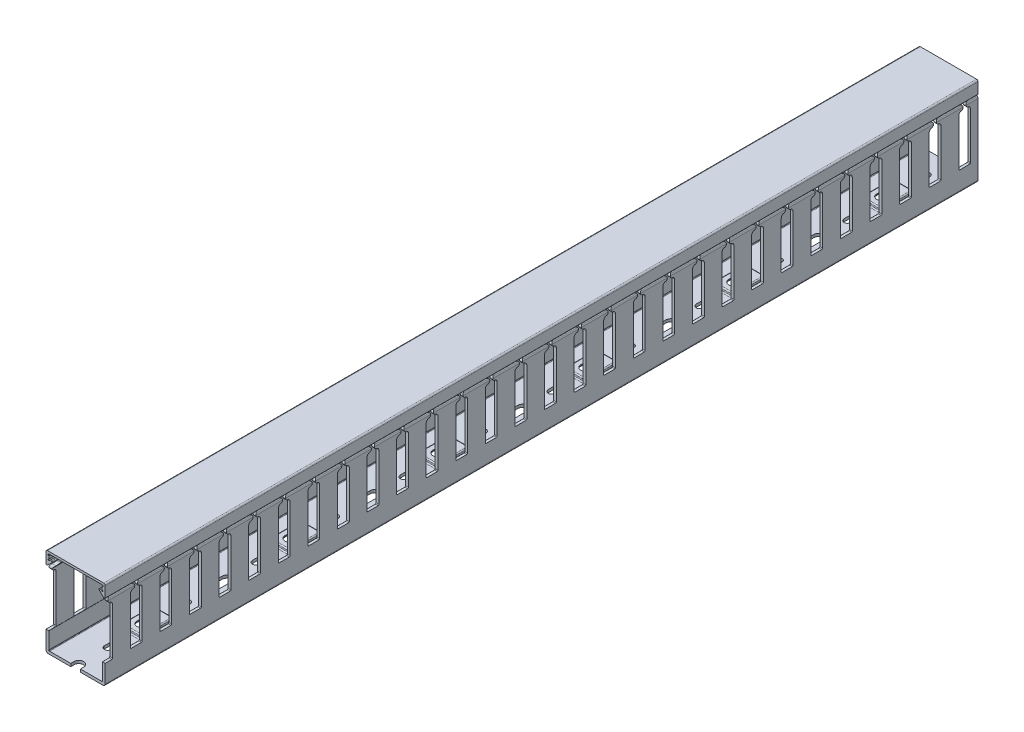
SolidWorks part; units mm, degrees
ref_plane "Front Plane" through (0, 0, 0) normal (0, 0, 1) x (1, 0, 0)
ref_plane "Top Plane" through (0, 0, 0) normal (0, 1, 0) x (1, 0, 0)
ref_plane "Right Plane" through (0, 0, 0) normal (1, 0, 0) x (0, 0, -1)
sketch "Sketch1" plane through (0, 0, 0) normal (0, 0, 1) x (1, 0, 0)
  line L0 (-18.2, -27.85) -> (-17.973, -27.983)
  line L1 (-20, -28.55) -> (-20, 19.1871)
  line L2 (-20, 21.7598) -> (-20, 29.05)
  line L3 (-18.5, 28.35) -> (-18.5, 27.55)
  line L4 (-18.5, 25.25) -> (-18.5, 25.058)
  line L5 (-19.6147, 20.1908) -> (-15.6798, 24.5609)
  line L6 (-17.8221, 24.7703) -> (-17.3671, 25.2097)
  line L7 (-15.9527, 24.4903) -> (-19.1527, 21.4001)
  line L8 (-18.1, 18.8416) -> (-18.1, -16.3923)
  line L9 (-18.1, -16.5077) -> (-18.1, -27.65)
  line L10 (-18, 25.55) -> (-18, 27.25)
  line L11 (-14.8603, 22.6316) -> (-17.9716, 19.1762)
  line L12 (-18.2, -16.45) -> (-18.1, -16.5077)
  line L13 (-13.3, 25.85) -> (-13.3, 24.6071)
  line L14 (-7, -28.15) -> (-7, -25.65)
  line L15 (-18.5, -30.05) -> (18.5, -30.05)
  line L16 (0, -30.05) -> (0, 30.05) construction
  line L18 (-17.6, -28.15) -> (17.6, -28.15)
  line L19 (-17.973, -27.983) -> (-17.973, -27.7208) construction
  line L20 (-18.082, -27.7829) -> (-17.973, -27.7208) construction
  line L21 (18.1, -16.5077) -> (18.1, -16.3923) construction
  line L23 (-7, -25.65) -> (7, -25.65)
  line L24 (-18.1, -16.5077) -> (-18.1, -16.3923) construction
  line L25 (-2.25, -30.05) -> (-2.25, -28.15)
  line L26 (2.25, -30.05) -> (2.25, -28.15)
  line L27 (7, -28.15) -> (7, -25.65)
  line L28 (17.973, -27.717) -> (18.082, -27.7829) construction
  line L29 (-18.1, -16.3923) -> (-18.2, -16.45)
  line L30 (18.1, -16.3923) -> (18.2, -16.45)
  line L31 (-18.082, -27.7829) -> (-18.2, -27.85)
  line L33 (18.4, 25.35) -> (18.2, 25.35)
  line L34 (-16.3, 25.35) -> (-17.0198, 25.35)
  line L35 (-18.4, 25.35) -> (-18.2, 25.35)
  line L36 (16.3, 25.35) -> (17.0198, 25.35)
  line L38 (-18.2, 27.45) -> (-18.4, 27.45)
  line L39 (18.2, 27.45) -> (18.4, 27.45)
  line L40 (16.0883, 27.65) -> (15.1, 27.65)
  line L41 (-16.0883, 27.65) -> (-15.1, 27.65)
  line L42 (-18.3, 28.55) -> (18.3, 28.55)
  line L44 (19, 30.05) -> (-19, 30.05)
  line L46 (-16.3812, 25.7055) -> (-17.6188, 25.3739)
  line L47 (16.3812, 25.7055) -> (17.6188, 25.3739)
  line L48 (13.3, 25.85) -> (13.3, 24.6071)
  line L49 (18, 25.55) -> (18, 27.25)
  line L50 (18.1, 18.8416) -> (18.1, -16.3923)
  line L51 (18.1, -16.5077) -> (18.1, -27.65)
  line L52 (18.5, 28.35) -> (18.5, 27.55)
  line L53 (18.5, 25.25) -> (18.5, 25.058)
  line L54 (18.2, -16.45) -> (18.1, -16.5077)
  line L55 (14.8603, 22.6316) -> (17.9716, 19.1762)
  line L56 (20, -28.55) -> (20, 19.1871)
  line L57 (20, 21.7598) -> (20, 29.05)
  line L58 (15.9527, 24.4903) -> (19.1527, 21.4001)
  line L59 (17.8221, 24.7703) -> (17.3671, 25.2097)
  line L60 (19.6147, 20.1908) -> (15.6798, 24.5609)
  line L61 (18.2, -27.85) -> (17.973, -27.983)
  line L62 (-2.25, -29.1) -> (2.25, -29.1) construction
  line L63 (-7, -26.9) -> (7, -26.9) construction
  line L64 (0, -29.1) -> (0, -26.9) construction
  line L68 (17.973, -27.983) -> (17.973, -27.717) construction
  line L69 (20, -4.6815) -> (18.1, -4.6815) construction
  line L70 (-20, -4.6815) -> (-18.1, -4.6815) construction
  line L71 (18.082, -27.7829) -> (18.2, -27.85)
  line L72 (16.4159, 20.9039) -> (17.8279, 22.1752) construction
  line L73 (18.2, -27.85) -> (17.973, -27.85) construction
  line L74 (20, 19.1871) -> (20, 19.7629) construction
  line L75 (20, 19.7629) -> (19.6147, 20.1908) construction
  line L76 (18.1, 18.8416) -> (18.1, 19.0335) construction
  line L77 (18.1, 19.0335) -> (17.9716, 19.1762) construction
  line L78 (20, 21.7598) -> (20, 20.5819) construction
  line L79 (20, 20.5819) -> (19.1527, 21.4001) construction
  line L80 (18.3, 28.55) -> (18.3, 30.05) construction
  line L81 (18.5, 28.35) -> (20, 28.35) construction
  line L82 (17.5946, 24.99) -> (16.5526, 23.911) construction
  line L83 (14.0985, 26.3171) -> (16.3812, 25.7055) construction
  line L84 (14.0985, 26.3171) -> (15.6798, 24.5609) construction
  line L85 (15.1, 24.6071) -> (15.1, 25.85) construction
  line L86 (15.1, 25.85) -> (16.0883, 25.85) construction
  line L87 (16.0883, 25.85) -> (16.0883, 24.6071) construction
  line L88 (16.0883, 24.6071) -> (15.1, 24.6071) construction
  arc A0 (-20, -28.55) -> (-18.5, -30.05) centre (-18.5, -28.55) ccw
  arc A1 (-18.1, -27.65) -> (-18.082, -27.7829) centre (-17.6, -27.65) ccw
  arc A2 (-17.973, -27.983) -> (-17.6, -28.15) centre (-17.6, -27.65) ccw
  arc A3 (-17.5208, 26.94) -> (-18.1276, 26.6686) centre (-15.7875, 22.25) ccw
  arc A4 (-14.8603, 22.6316) -> (-13.7623, 23.4026) centre (-15.9918, 25.41) ccw
  arc A5 (-16.0883, 27.65) -> (-17.5208, 26.94) centre (-16.0883, 25.85) ccw
  arc A6 (-13.3, 25.85) -> (-15.1, 27.65) centre (-15.1, 25.85) ccw
  arc A7 (-13.7623, 23.4026) -> (-13.3, 24.6071) centre (-15.1, 24.6071) ccw
  arc A8 (-19.6147, 20.1908) -> (-20, 19.1871) centre (-18.5, 19.1871) ccw
  arc A9 (-19, 30.05) -> (-20, 29.05) centre (-19, 29.05) ccw
  arc A10 (-15.6798, 24.5609) -> (-16.3812, 25.7055) centre (-16.2, 25.0293) ccw
  arc A11 (-18.1276, 26.6686) -> (-17.6188, 25.3739) centre (-17.8, 26.05) ccw
  arc A12 (-17.0198, 25.35) -> (-17.3671, 25.2097) centre (-17.0198, 24.85) ccw
  arc A13 (-15.9527, 24.4903) -> (-16.3, 25.35) centre (-16.3, 24.85) ccw
  arc A14 (-20, 21.7598) -> (-19.1527, 21.4001) centre (-19.5, 21.7598) ccw
  arc A15 (-17.9716, 19.1762) -> (-18.1, 18.8416) centre (-17.6, 18.8416) ccw
  arc A16 (-18.5, 25.058) -> (-17.8221, 24.7703) centre (-18.1, 25.058) ccw
  arc A17 (-18.3, 28.55) -> (-18.5, 28.35) centre (-18.3, 28.35) ccw
  arc A18 (-18, 27.25) -> (-18.2, 27.45) centre (-18.2, 27.25) ccw
  arc A19 (-18.2, 25.35) -> (-18, 25.55) centre (-18.2, 25.55) ccw
  arc A20 (-18.4, 25.35) -> (-18.5, 25.25) centre (-18.4, 25.25) ccw
  arc A21 (-18.5, 27.55) -> (-18.4, 27.45) centre (-18.4, 27.55) ccw
  arc A22 (18.5, -30.05) -> (20, -28.55) centre (18.5, -28.55) ccw
  arc A23 (17.6, -28.15) -> (17.973, -27.983) centre (17.6, -27.65) ccw
  arc A24 (18.082, -27.7829) -> (18.1, -27.65) centre (17.6, -27.65) ccw
  arc A25 (18.1276, 26.6686) -> (17.5208, 26.94) centre (15.7875, 22.25) ccw
  arc A26 (13.7623, 23.4026) -> (14.8603, 22.6316) centre (15.9918, 25.41) ccw
  arc A27 (13.3, 24.6071) -> (13.7623, 23.4026) centre (15.1, 24.6071) ccw
  arc A28 (15.1, 27.65) -> (13.3, 25.85) centre (15.1, 25.85) ccw
  arc A29 (17.5208, 26.94) -> (16.0883, 27.65) centre (16.0883, 25.85) ccw
  arc A30 (20, 19.1871) -> (19.6147, 20.1908) centre (18.5, 19.1871) ccw
  arc A31 (20, 29.05) -> (19, 30.05) centre (19, 29.05) ccw
  arc A32 (17.6188, 25.3739) -> (18.1276, 26.6686) centre (17.8, 26.05) ccw
  arc A33 (16.3812, 25.7055) -> (15.6798, 24.5609) centre (16.2, 25.0293) ccw
  arc A34 (17.3671, 25.2097) -> (17.0198, 25.35) centre (17.0198, 24.85) ccw
  arc A35 (16.3, 25.35) -> (15.9527, 24.4903) centre (16.3, 24.85) ccw
  arc A36 (19.1527, 21.4001) -> (20, 21.7598) centre (19.5, 21.7598) ccw
  arc A37 (18.1, 18.8416) -> (17.9716, 19.1762) centre (17.6, 18.8416) ccw
  arc A38 (17.8221, 24.7703) -> (18.5, 25.058) centre (18.1, 25.058) ccw
  arc A39 (18.5, 28.35) -> (18.3, 28.55) centre (18.3, 28.35) ccw
  arc A40 (18.2, 27.45) -> (18, 27.25) centre (18.2, 27.25) ccw
  arc A41 (18, 25.55) -> (18.2, 25.35) centre (18.2, 25.55) ccw
  arc A42 (18.5, 25.25) -> (18.4, 25.35) centre (18.4, 25.25) ccw
  arc A43 (18.4, 27.45) -> (18.5, 27.55) centre (18.4, 27.55) ccw
  point P188 (0, 28.55)
  dimension "D2" = 1.5
  dimension "D9" = 0.5
  dimension "D12" = 1
  dimension "D13" = 1.8
  dimension "D14" = 0.2
  dimension "D15" = 0.1
  dimension "D16" = 0.7
  dimension "D28" = 0.4
  dimension "D29" = 3
  dimension "D30" = 5
  dimension "D1" = 14
  dimension "Height" = 60.1
  dimension "Width" = 40
  dimension "D3" = 1.9
  dimension "D4" = 1.5
  dimension "D5" = 0.1155
  dimension "D6" = 46
  dimension "D7" = 138
  dimension "D10" = 2.5
  dimension "D11" = 4.5
  dimension "D18" = 0.3
  dimension "D19" = 0.266
  dimension "D20" = 60
  dimension "D21" = 8.6165
  dimension "D22" = 9.4681
  dimension "D23" = 0.5
  dimension "D24" = 1.1
  dimension "D25" = 2.1
  dimension "D26" = 0.9
  dimension "D27" = 4.8
  dimension "D31" = 0.9883
  dimension "D32" = 1.2429
  dimension "D33" = 33
  dimension "D34" = 5.0184
  dimension "D35" = 4.2208
  dimension "Slot Height" = 13.6
sketch "Sketch2" plane through (0, 0, 0) normal (0, 1, 0) x (1, 0, 0)
  line L1 (-20, 295) -> (20, 295)
  line L2 (-20, 295) -> (-20, -295)
  line L3 (-20, -295) -> (20, -295)
  line L4 (20, 295) -> (20, -295)
  line L5 (-20, 295) -> (20, -295) construction
  line L6 (-20, -295) -> (20, 295) construction
  line L9 (0, -300.25) -> (0, -292.75) construction
  line L10 (-3.25, -300.25) -> (-3.25, -292.75)
  line L11 (3.25, -300.25) -> (3.25, -292.75)
  line L15 (0, -289.5) -> (0, -292.75) construction
  line L16 (0, -300.25) -> (0, -303.5) construction
  line L17 (0, -273.25) -> (0, -269.75) construction
  line L18 (-2.25, -273.25) -> (-2.25, -269.75)
  line L19 (2.25, -273.25) -> (2.25, -269.75)
  line L23 (0, -273.25) -> (0, -275.5) construction
  line L24 (0, -250.25) -> (0, -242.75) construction
  line L26 (0, -269.75) -> (0, -267.5) construction
  line L30 (7, -257.2071) -> (-7, -257.2071)
  line L31 (7, -257.2071) -> (7, -235.7929)
  line L32 (7, -235.7929) -> (-7, -235.7929)
  line L33 (-7, -257.2071) -> (-7, -235.7929)
  line L34 (-3.25, -250.25) -> (-3.25, -242.75)
  line L35 (3.25, -250.25) -> (3.25, -242.75)
  line L36 (0, -200.25) -> (0, -192.75) construction
  line L37 (-3.25, -200.25) -> (-3.25, -192.75)
  line L38 (3.25, -200.25) -> (3.25, -192.75)
  line L45 (0, -223.25) -> (0, -219.75) construction
  line L46 (-2.25, -223.25) -> (-2.25, -219.75)
  line L47 (2.25, -223.25) -> (2.25, -219.75)
  arc A2 (-3.25, -300.25) -> (3.25, -300.25) centre (0, -300.25) ccw
  arc A3 (3.25, -292.75) -> (-3.25, -292.75) centre (0, -292.75) ccw
  arc A6 (-2.25, -273.25) -> (2.25, -273.25) centre (0, -273.25) ccw
  arc A7 (2.25, -269.75) -> (-2.25, -269.75) centre (0, -269.75) ccw
  arc A10 (-3.25, -250.25) -> (3.25, -250.25) centre (0, -250.25) ccw
  arc A11 (3.25, -242.75) -> (-3.25, -242.75) centre (0, -242.75) ccw
  arc A12 (-3.25, -200.25) -> (3.25, -200.25) centre (0, -200.25) ccw
  arc A13 (3.25, -192.75) -> (-3.25, -192.75) centre (0, -192.75) ccw
  arc A18 (-2.25, -223.25) -> (2.25, -223.25) centre (0, -223.25) ccw
  arc A19 (2.25, -219.75) -> (-2.25, -219.75) centre (0, -219.75) ccw
  point P0 (0, 0)
  point P14 (0, -296.5)
  point P33 (0, -271.5)
  point P67 (0, -246.5)
  point P74 (-7, -246.5)
  point P75 (0, -196.5)
  point P96 (0, -221.5)
  dimension "D1" = 5.5
  dimension "D2" = 14
  dimension "Length" = 590
  dimension "D3" = 6.5
  dimension "D4" = 8
  dimension "D5" = 23.5
  dimension "D6" = 21.4142
  dimension "D7" = 25
  dimension "Slot Spacing 2" = 100
  dimension "Slot Spacing 1" = 50
sketch "Sketch3" plane through (0, 0, 0) normal (0, 0, 1) x (1, 0, 0)
  line L0 (15.9527, 24.4903) -> (19.1527, 21.4001) construction
  line L1 (16.3, 25.35) -> (17.0198, 25.35) construction
  line L2 (17.8221, 24.7703) -> (17.3671, 25.2097) construction
  line L3 (18.5, 25.25) -> (18.5, 25.058) construction
  line L4 (18.4, 25.35) -> (18.2, 25.35) construction
  line L5 (18, 25.55) -> (18, 27.25) construction
  line L6 (18.2, 27.45) -> (18.4, 27.45) construction
  line L7 (18.5, 28.35) -> (18.5, 27.55) construction
  line L8 (20, 21.7598) -> (20, 29.05) construction
  line L9 (19, 30.05) -> (-19, 30.05) construction
  line L10 (-18.3, 28.55) -> (18.3, 28.55) construction
  line L11 (-18.5, 28.35) -> (-18.5, 27.55) construction
  line L12 (-18.2, 27.45) -> (-18.4, 27.45) construction
  line L13 (-18, 25.55) -> (-18, 27.25) construction
  line L14 (-18.4, 25.35) -> (-18.2, 25.35) construction
  line L15 (-18.5, 25.25) -> (-18.5, 25.058) construction
  line L16 (-17.8221, 24.7703) -> (-17.3671, 25.2097) construction
  line L17 (-16.3, 25.35) -> (-17.0198, 25.35) construction
  line L18 (-15.9527, 24.4903) -> (-19.1527, 21.4001) construction
  line L19 (-20, 21.7598) -> (-20, 29.05) construction
  line L20 (15.9527, 24.4903) -> (19.1527, 21.4001)
  line L21 (16.3, 25.35) -> (17.0198, 25.35)
  line L22 (17.8221, 24.7703) -> (17.3671, 25.2097)
  line L23 (18.5, 25.25) -> (18.5, 25.058)
  line L24 (18.4, 25.35) -> (18.2, 25.35)
  line L25 (18, 25.55) -> (18, 27.25)
  line L26 (18.2, 27.45) -> (18.4, 27.45)
  line L27 (18.5, 28.35) -> (18.5, 27.55)
  line L28 (20, 21.7598) -> (20, 29.05)
  line L29 (19, 30.05) -> (-19, 30.05)
  line L30 (-18.3, 28.55) -> (18.3, 28.55)
  line L31 (-18.5, 28.35) -> (-18.5, 27.55)
  line L32 (-18.2, 27.45) -> (-18.4, 27.45)
  line L33 (-18, 25.55) -> (-18, 27.25)
  line L34 (-18.4, 25.35) -> (-18.2, 25.35)
  line L35 (-18.5, 25.25) -> (-18.5, 25.058)
  line L36 (-17.8221, 24.7703) -> (-17.3671, 25.2097)
  line L37 (-16.3, 25.35) -> (-17.0198, 25.35)
  line L38 (-15.9527, 24.4903) -> (-19.1527, 21.4001)
  line L39 (-20, 21.7598) -> (-20, 29.05)
  arc A0 (19.1527, 21.4001) -> (20, 21.7598) centre (19.5, 21.7598) ccw construction
  arc A1 (16.3, 25.35) -> (15.9527, 24.4903) centre (16.3, 24.85) ccw construction
  arc A2 (17.3671, 25.2097) -> (17.0198, 25.35) centre (17.0198, 24.85) ccw construction
  arc A3 (17.8221, 24.7703) -> (18.5, 25.058) centre (18.1, 25.058) ccw construction
  arc A4 (18.5, 25.25) -> (18.4, 25.35) centre (18.4, 25.25) ccw construction
  arc A5 (18, 25.55) -> (18.2, 25.35) centre (18.2, 25.55) ccw construction
  arc A6 (18.2, 27.45) -> (18, 27.25) centre (18.2, 27.25) ccw construction
  arc A7 (18.4, 27.45) -> (18.5, 27.55) centre (18.4, 27.55) ccw construction
  arc A8 (18.5, 28.35) -> (18.3, 28.55) centre (18.3, 28.35) ccw construction
  arc A9 (20, 29.05) -> (19, 30.05) centre (19, 29.05) ccw construction
  arc A10 (-18.3, 28.55) -> (-18.5, 28.35) centre (-18.3, 28.35) ccw construction
  arc A11 (-18.5, 27.55) -> (-18.4, 27.45) centre (-18.4, 27.55) ccw construction
  arc A12 (-18, 27.25) -> (-18.2, 27.45) centre (-18.2, 27.25) ccw construction
  arc A13 (-18.2, 25.35) -> (-18, 25.55) centre (-18.2, 25.55) ccw construction
  arc A14 (-18.4, 25.35) -> (-18.5, 25.25) centre (-18.4, 25.25) ccw construction
  arc A15 (-18.5, 25.058) -> (-17.8221, 24.7703) centre (-18.1, 25.058) ccw construction
  arc A16 (-17.0198, 25.35) -> (-17.3671, 25.2097) centre (-17.0198, 24.85) ccw construction
  arc A17 (-15.9527, 24.4903) -> (-16.3, 25.35) centre (-16.3, 24.85) ccw construction
  arc A18 (-20, 21.7598) -> (-19.1527, 21.4001) centre (-19.5, 21.7598) ccw construction
  arc A19 (-19, 30.05) -> (-20, 29.05) centre (-19, 29.05) ccw construction
  arc A20 (19.1527, 21.4001) -> (20, 21.7598) centre (19.5, 21.7598) ccw
  arc A21 (16.3, 25.35) -> (15.9527, 24.4903) centre (16.3, 24.85) ccw
  arc A22 (17.3671, 25.2097) -> (17.0198, 25.35) centre (17.0198, 24.85) ccw
  arc A23 (17.8221, 24.7703) -> (18.5, 25.058) centre (18.1, 25.058) ccw
  arc A24 (18.5, 25.25) -> (18.4, 25.35) centre (18.4, 25.25) ccw
  arc A25 (18, 25.55) -> (18.2, 25.35) centre (18.2, 25.55) ccw
  arc A26 (18.2, 27.45) -> (18, 27.25) centre (18.2, 27.25) ccw
  arc A27 (18.4, 27.45) -> (18.5, 27.55) centre (18.4, 27.55) ccw
  arc A28 (18.5, 28.35) -> (18.3, 28.55) centre (18.3, 28.35) ccw
  arc A29 (20, 29.05) -> (19, 30.05) centre (19, 29.05) ccw
  arc A30 (-18.3, 28.55) -> (-18.5, 28.35) centre (-18.3, 28.35) ccw
  arc A31 (-18.5, 27.55) -> (-18.4, 27.45) centre (-18.4, 27.55) ccw
  arc A32 (-18, 27.25) -> (-18.2, 27.45) centre (-18.2, 27.25) ccw
  arc A33 (-18.2, 25.35) -> (-18, 25.55) centre (-18.2, 25.55) ccw
  arc A34 (-18.4, 25.35) -> (-18.5, 25.25) centre (-18.4, 25.25) ccw
  arc A35 (-18.5, 25.058) -> (-17.8221, 24.7703) centre (-18.1, 25.058) ccw
  arc A36 (-17.0198, 25.35) -> (-17.3671, 25.2097) centre (-17.0198, 24.85) ccw
  arc A37 (-15.9527, 24.4903) -> (-16.3, 25.35) centre (-16.3, 24.85) ccw
  arc A38 (-20, 21.7598) -> (-19.1527, 21.4001) centre (-19.5, 21.7598) ccw
  arc A39 (-19, 30.05) -> (-20, 29.05) centre (-19, 29.05) ccw
extrude "Boss-Extrude1" add sketch "Sketch3" along normal up to vertex (295 mm away) from vertex separate body up to point (20, 0, 295) starting at point (20, 0, -295)
sketch "Sketch4" plane through (0, 0, 0) normal (0, 0, 1) x (1, 0, 0)
  line L0 (18.2, -27.85) -> (17.973, -27.983) construction
  line L1 (18.082, -27.7829) -> (18.2, -27.85) construction
  line L2 (18.1, -16.5077) -> (18.1, -27.65) construction
  line L3 (18.2, -16.45) -> (18.1, -16.5077) construction
  line L4 (18.1, -16.3923) -> (18.2, -16.45) construction
  line L5 (20, -28.55) -> (20, 19.1871) construction
  line L6 (18.1, 18.8416) -> (18.1, -16.3923) construction
  line L7 (19.6147, 20.1908) -> (15.6798, 24.5609) construction
  line L8 (16.3812, 25.7055) -> (17.6188, 25.3739) construction
  line L9 (14.8603, 22.6316) -> (17.9716, 19.1762) construction
  line L10 (13.3, 25.85) -> (13.3, 24.6071) construction
  line L11 (16.0883, 27.65) -> (15.1, 27.65) construction
  line L12 (-16.3812, 25.7055) -> (-17.6188, 25.3739) construction
  line L13 (-16.0883, 27.65) -> (-15.1, 27.65) construction
  line L14 (-13.3, 25.85) -> (-13.3, 24.6071) construction
  line L15 (-19.6147, 20.1908) -> (-15.6798, 24.5609) construction
  line L16 (-14.8603, 22.6316) -> (-17.9716, 19.1762) construction
  line L17 (-18.1, 18.8416) -> (-18.1, -16.3923) construction
  line L18 (-18.1, -16.3923) -> (-18.2, -16.45) construction
  line L19 (-18.2, -16.45) -> (-18.1, -16.5077) construction
  line L20 (-18.1, -16.5077) -> (-18.1, -27.65) construction
  line L21 (-18.082, -27.7829) -> (-18.2, -27.85) construction
  line L22 (-18.2, -27.85) -> (-17.973, -27.983) construction
  line L23 (-17.6, -28.15) -> (17.6, -28.15) construction
  line L24 (-18.5, -30.05) -> (18.5, -30.05) construction
  line L25 (-20, -28.55) -> (-20, 19.1871) construction
  line L26 (18.2, -27.85) -> (17.973, -27.983)
  line L27 (18.082, -27.7829) -> (18.2, -27.85)
  line L28 (18.1, -16.5077) -> (18.1, -27.65)
  line L29 (18.2, -16.45) -> (18.1, -16.5077)
  line L30 (18.1, -16.3923) -> (18.2, -16.45)
  line L31 (20, -28.55) -> (20, 19.1871)
  line L32 (18.1, 18.8416) -> (18.1, -16.3923)
  line L33 (19.6147, 20.1908) -> (15.6798, 24.5609)
  line L34 (16.3812, 25.7055) -> (17.6188, 25.3739)
  line L35 (14.8603, 22.6316) -> (17.9716, 19.1762)
  line L36 (13.3, 25.85) -> (13.3, 24.6071)
  line L37 (16.0883, 27.65) -> (15.1, 27.65)
  line L38 (-16.3812, 25.7055) -> (-17.6188, 25.3739)
  line L39 (-16.0883, 27.65) -> (-15.1, 27.65)
  line L40 (-13.3, 25.85) -> (-13.3, 24.6071)
  line L41 (-19.6147, 20.1908) -> (-15.6798, 24.5609)
  line L42 (-14.8603, 22.6316) -> (-17.9716, 19.1762)
  line L43 (-18.1, 18.8416) -> (-18.1, -16.3923)
  line L44 (-18.1, -16.3923) -> (-18.2, -16.45)
  line L45 (-18.2, -16.45) -> (-18.1, -16.5077)
  line L46 (-18.1, -16.5077) -> (-18.1, -27.65)
  line L47 (-18.082, -27.7829) -> (-18.2, -27.85)
  line L48 (-18.2, -27.85) -> (-17.973, -27.983)
  line L49 (-17.6, -28.15) -> (17.6, -28.15)
  line L50 (-18.5, -30.05) -> (18.5, -30.05)
  line L51 (-20, -28.55) -> (-20, 19.1871)
  arc A0 (18.5, -30.05) -> (20, -28.55) centre (18.5, -28.55) ccw construction
  arc A1 (17.6, -28.15) -> (17.973, -27.983) centre (17.6, -27.65) ccw construction
  arc A2 (18.082, -27.7829) -> (18.1, -27.65) centre (17.6, -27.65) ccw construction
  arc A3 (18.1, 18.8416) -> (17.9716, 19.1762) centre (17.6, 18.8416) ccw construction
  arc A4 (20, 19.1871) -> (19.6147, 20.1908) centre (18.5, 19.1871) ccw construction
  arc A5 (16.3812, 25.7055) -> (15.6798, 24.5609) centre (16.2, 25.0293) ccw construction
  arc A6 (13.7623, 23.4026) -> (14.8603, 22.6316) centre (15.9918, 25.41) ccw construction
  arc A7 (13.3, 24.6071) -> (13.7623, 23.4026) centre (15.1, 24.6071) ccw construction
  arc A8 (15.1, 27.65) -> (13.3, 25.85) centre (15.1, 25.85) ccw construction
  arc A9 (17.5208, 26.94) -> (16.0883, 27.65) centre (16.0883, 25.85) ccw construction
  arc A10 (18.1276, 26.6686) -> (17.5208, 26.94) centre (15.7875, 22.25) ccw construction
  arc A11 (17.6188, 25.3739) -> (18.1276, 26.6686) centre (17.8, 26.05) ccw construction
  arc A12 (-15.6798, 24.5609) -> (-16.3812, 25.7055) centre (-16.2, 25.0293) ccw construction
  arc A13 (-18.1276, 26.6686) -> (-17.6188, 25.3739) centre (-17.8, 26.05) ccw construction
  arc A14 (-17.5208, 26.94) -> (-18.1276, 26.6686) centre (-15.7875, 22.25) ccw construction
  arc A15 (-16.0883, 27.65) -> (-17.5208, 26.94) centre (-16.0883, 25.85) ccw construction
  arc A16 (-13.3, 25.85) -> (-15.1, 27.65) centre (-15.1, 25.85) ccw construction
  arc A17 (-13.7623, 23.4026) -> (-13.3, 24.6071) centre (-15.1, 24.6071) ccw construction
  arc A18 (-14.8603, 22.6316) -> (-13.7623, 23.4026) centre (-15.9918, 25.41) ccw construction
  arc A19 (-17.9716, 19.1762) -> (-18.1, 18.8416) centre (-17.6, 18.8416) ccw construction
  arc A20 (-19.6147, 20.1908) -> (-20, 19.1871) centre (-18.5, 19.1871) ccw construction
  arc A21 (-18.1, -27.65) -> (-18.082, -27.7829) centre (-17.6, -27.65) ccw construction
  arc A22 (-17.973, -27.983) -> (-17.6, -28.15) centre (-17.6, -27.65) ccw construction
  arc A23 (-20, -28.55) -> (-18.5, -30.05) centre (-18.5, -28.55) ccw construction
  arc A24 (18.5, -30.05) -> (20, -28.55) centre (18.5, -28.55) ccw
  arc A25 (17.6, -28.15) -> (17.973, -27.983) centre (17.6, -27.65) ccw
  arc A26 (18.082, -27.7829) -> (18.1, -27.65) centre (17.6, -27.65) ccw
  arc A27 (18.1, 18.8416) -> (17.9716, 19.1762) centre (17.6, 18.8416) ccw
  arc A28 (20, 19.1871) -> (19.6147, 20.1908) centre (18.5, 19.1871) ccw
  arc A29 (16.3812, 25.7055) -> (15.6798, 24.5609) centre (16.2, 25.0293) ccw
  arc A30 (13.7623, 23.4026) -> (14.8603, 22.6316) centre (15.9918, 25.41) ccw
  arc A31 (13.3, 24.6071) -> (13.7623, 23.4026) centre (15.1, 24.6071) ccw
  arc A32 (15.1, 27.65) -> (13.3, 25.85) centre (15.1, 25.85) ccw
  arc A33 (17.5208, 26.94) -> (16.0883, 27.65) centre (16.0883, 25.85) ccw
  arc A34 (18.1276, 26.6686) -> (17.5208, 26.94) centre (15.7875, 22.25) ccw
  arc A35 (17.6188, 25.3739) -> (18.1276, 26.6686) centre (17.8, 26.05) ccw
  arc A36 (-15.6798, 24.5609) -> (-16.3812, 25.7055) centre (-16.2, 25.0293) ccw
  arc A37 (-18.1276, 26.6686) -> (-17.6188, 25.3739) centre (-17.8, 26.05) ccw
  arc A38 (-17.5208, 26.94) -> (-18.1276, 26.6686) centre (-15.7875, 22.25) ccw
  arc A39 (-16.0883, 27.65) -> (-17.5208, 26.94) centre (-16.0883, 25.85) ccw
  arc A40 (-13.3, 25.85) -> (-15.1, 27.65) centre (-15.1, 25.85) ccw
  arc A41 (-13.7623, 23.4026) -> (-13.3, 24.6071) centre (-15.1, 24.6071) ccw
  arc A42 (-14.8603, 22.6316) -> (-13.7623, 23.4026) centre (-15.9918, 25.41) ccw
  arc A43 (-17.9716, 19.1762) -> (-18.1, 18.8416) centre (-17.6, 18.8416) ccw
  arc A44 (-19.6147, 20.1908) -> (-20, 19.1871) centre (-18.5, 19.1871) ccw
  arc A45 (-18.1, -27.65) -> (-18.082, -27.7829) centre (-17.6, -27.65) ccw
  arc A46 (-17.973, -27.983) -> (-17.6, -28.15) centre (-17.6, -27.65) ccw
  arc A47 (-20, -28.55) -> (-18.5, -30.05) centre (-18.5, -28.55) ccw
extrude "Boss-Extrude2" add sketch "Sketch4" along normal up to vertex (295 mm away) from vertex separate body up to point (20, 0, 295) starting at point (20, 0, -295)
sketch "Sketch5" plane through (0, 0, 0) normal (0, 1, 0) x (1, 0, 0)
  line L4 (7, -235.7929) -> (-7, -235.7929) construction
  line L5 (7, -257.2071) -> (7, -235.7929) construction
  line L6 (7, -257.2071) -> (-7, -257.2071) construction
  line L7 (-7, -257.2071) -> (-7, -235.7929) construction
  line L12 (7, -235.7929) -> (-7, -235.7929)
  line L13 (7, -257.2071) -> (7, -235.7929)
  line L14 (7, -257.2071) -> (-7, -257.2071)
  line L15 (-7, -257.2071) -> (-7, -235.7929)
extrude "Boss-Extrude3" add sketch "Sketch5" along normal up to vertex (-25.65 mm away) from vertex up to point (7, -25.65, 0) starting at point (0, -30.05, 0)
sketch "Sketch6" plane through (0, 0, 0) normal (0, 1, 0) x (1, 0, 0)
  line L4 (-7, -257.2071) -> (-7, -235.7929) construction
  line L5 (7, -235.7929) -> (-7, -235.7929) construction
  line L6 (7, -257.2071) -> (7, -235.7929) construction
  line L7 (7, -257.2071) -> (-7, -257.2071) construction
  line L12 (-7, -257.2071) -> (-7, -235.7929) construction
  line L13 (7, -235.7929) -> (-7, -235.7929) construction
  line L14 (7, -257.2071) -> (7, -235.7929) construction
  line L15 (7, -257.2071) -> (-7, -257.2071) construction
  line L16 (6.268, -256.4751) -> (6.268, -236.5249)
  line L17 (6.268, -236.5249) -> (-6.268, -236.5249)
  line L18 (-6.268, -256.4751) -> (-6.268, -236.5249)
  line L19 (6.268, -256.4751) -> (-6.268, -256.4751)
  dimension "D1" = 0.732
extrude "Cut-Extrude1" cut sketch "Sketch6" along normal blind 3.6678 from vertex starting at point (0, -30.05, 0)
fillet "Fillet1" radius 0.732 24 edges at (0, -28.15, 235.7929) (7, -26.9, 235.7929) (7, -28.15, 246.5) (-7, -28.15, 246.5) (-7, -26.9, 235.7929) (7, -26.9, 257.2071) (0, -28.15, 257.2071) (-7, -26.9, 257.2071) (0, -25.65, 257.2071) (-7, -25.65, 246.5) (0, -25.65, 235.7929) (7, -25.65, 246.5) (0, -26.3822, 236.5249) (0, -30.05, 236.5249) (-6.268, -26.3822, 246.5) (-6.268, -30.05, 246.5) (0, -26.3822, 256.4751) (0, -30.05, 256.4751) (6.268, -26.3822, 246.5) (6.268, -30.05, 246.5) (-6.268, -28.2161, 236.5249) (-6.268, -28.2161, 256.4751) (6.268, -28.2161, 236.5249) (6.268, -28.2161, 256.4751)
pattern_linear "LPattern1" count 6 spacing 100 along (0, 0, -1) of "Boss-Extrude3", "Cut-Extrude1", "Fillet1"
sketch "Sketch7" plane through (0, 0, 0) normal (0, 1, 0) x (1, 0, 0)
  line L4 (-2.25, -223.25) -> (-2.25, -219.75) construction
  line L6 (-3.25, -250.25) -> (-3.25, -242.75) construction
  line L7 (-2.25, -273.25) -> (-2.25, -269.75) construction
  line L10 (-3.25, -300.25) -> (-3.25, -292.75) construction
  line L16 (-2.25, -223.25) -> (-2.25, -219.75)
  line L18 (-3.25, -250.25) -> (-3.25, -242.75)
  line L19 (-2.25, -273.25) -> (-2.25, -269.75)
  line L22 (-3.25, -300.25) -> (-3.25, -292.75)
  line L28 (2.25, -223.25) -> (2.25, -219.75) construction
  line L30 (3.25, -250.25) -> (3.25, -242.75) construction
  line L31 (2.25, -273.25) -> (2.25, -269.75) construction
  line L34 (3.25, -300.25) -> (3.25, -292.75) construction
  line L40 (2.25, -223.25) -> (2.25, -219.75)
  line L42 (3.25, -250.25) -> (3.25, -242.75)
  line L43 (2.25, -273.25) -> (2.25, -269.75)
  line L46 (3.25, -300.25) -> (3.25, -292.75)
  line L54 (0, -271.5) -> (0, -221.5) construction
  arc A8 (-2.25, -223.25) -> (2.25, -223.25) centre (0, -223.25) ccw construction
  arc A9 (2.25, -219.75) -> (-2.25, -219.75) centre (0, -219.75) ccw construction
  arc A12 (-3.25, -250.25) -> (3.25, -250.25) centre (0, -250.25) ccw construction
  arc A13 (3.25, -242.75) -> (-3.25, -242.75) centre (0, -242.75) ccw construction
  arc A14 (-2.25, -273.25) -> (2.25, -273.25) centre (0, -273.25) ccw construction
  arc A15 (2.25, -269.75) -> (-2.25, -269.75) centre (0, -269.75) ccw construction
  arc A20 (-3.25, -300.25) -> (3.25, -300.25) centre (0, -300.25) ccw construction
  arc A21 (3.25, -292.75) -> (-3.25, -292.75) centre (0, -292.75) ccw construction
  arc A32 (-2.25, -223.25) -> (2.25, -223.25) centre (0, -223.25) ccw
  arc A33 (2.25, -219.75) -> (-2.25, -219.75) centre (0, -219.75) ccw
  arc A36 (-3.25, -250.25) -> (3.25, -250.25) centre (0, -250.25) ccw
  arc A37 (3.25, -242.75) -> (-3.25, -242.75) centre (0, -242.75) ccw
  arc A38 (-2.25, -273.25) -> (2.25, -273.25) centre (0, -273.25) ccw
  arc A39 (2.25, -269.75) -> (-2.25, -269.75) centre (0, -269.75) ccw
  arc A44 (-3.25, -300.25) -> (3.25, -300.25) centre (0, -300.25) ccw
  arc A45 (3.25, -292.75) -> (-3.25, -292.75) centre (0, -292.75) ccw
extrude "Cut-Extrude2" cut sketch "Sketch7" against normal through all both and the other way through all
pattern_linear "LPattern2" count 7 spacing 100 along (0, 0, -1) of "Cut-Extrude2"
sketch "Sketch8" plane through (0, 0, 0) normal (1, 0, 0) x (0, 0, -1)
  line L0 (-298, 15.6859) -> (-298, -15.95)
  line L1 (-290, -15.95) -> (-290, 15.6859)
  line L2 (-296, 15.6859) -> (-292, 15.6859) construction
  line L3 (-297.5, -16.45) -> (-290.5, -16.45)
  line L4 (-292, 15.6859) -> (-292, 22.6141) construction
  line L5 (-292, 22.6141) -> (-296, 22.6141) construction
  line L6 (-298, 51.2859) -> (-298, 22.6141)
  line L7 (-290, 22.6141) -> (-290, 51.2859)
  line L9 (-296.5, 19.15) -> (-291.5, 19.15) construction
  line L11 (-296, 22.6141) -> (-296, 15.6859) construction
  line L13 (-298, 36.95) -> (-290, 36.95) construction
  line L15 (-298, 58.2141) -> (-298, 90.35)
  line L16 (-298, 90.35) -> (-290, 90.35)
  line L17 (-290, 90.35) -> (-290, 58.2141)
  line L18 (-291.5, 19.15) -> (-291.5, 54.75) construction
  line L19 (-291.5, 54.75) -> (-291.5, 90.35) construction
  line L20 (-291.5, 19.15) -> (-291.5, -16.45) construction
  arc A2 (-290.5, -16.45) -> (-290, -15.95) centre (-290.5, -15.95) ccw
  arc A3 (-298, -15.95) -> (-297.5, -16.45) centre (-297.5, -15.95) ccw
  arc A4 (-296.2857, 17.6654) -> (-298, 15.6859) centre (-296, 15.6859) ccw
  arc A5 (-298, 22.6141) -> (-296.2857, 20.6346) centre (-296, 22.6141) ccw
  arc A6 (-296.2857, 17.6654) -> (-296.2857, 20.6346) centre (-296.5, 19.15) ccw
  arc A9 (-291.7143, 17.6654) -> (-290, 15.6859) centre (-292, 15.6859) cw
  arc A11 (-291.7143, 17.6654) -> (-291.7143, 20.6346) centre (-291.5, 19.15) cw
  arc A14 (-290, 22.6141) -> (-291.7143, 20.6346) centre (-292, 22.6141) cw
  arc A15 (-290, 51.2859) -> (-291.7143, 53.2654) centre (-292, 51.2859) ccw
  arc A16 (-291.7143, 56.2346) -> (-291.7143, 53.2654) centre (-291.5, 54.75) ccw
  arc A17 (-291.7143, 56.2346) -> (-290, 58.2141) centre (-292, 58.2141) ccw
  arc A18 (-296.2857, 56.2346) -> (-298, 58.2141) centre (-296, 58.2141) cw
  arc A19 (-296.2857, 56.2346) -> (-296.2857, 53.2654) centre (-296.5, 54.75) cw
  arc A20 (-298, 51.2859) -> (-296.2857, 53.2654) centre (-296, 51.2859) cw
  point P36 (-214, -16.45)
  point P38 (-294, -16.45)
  point P40 (-234, -16.45)
  point P42 (-293, 19.15)
  point P45 (-295, 19.15)
  dimension "D3" = 0.5
  dimension "D4" = 2
  dimension "D5" = 1.5
  dimension "D1" = 8
  dimension "D2" = 6.9282
  dimension "D6" = 80
  dimension "D7" = 2
  dimension "D8" = 20
  dimension "Wire Slot Height Space" = 35.6
extrude "Cut-Extrude3" cut sketch "Sketch8" against normal through all both and the other way through all
pattern_linear "LPattern4" count 32 spacing 20 along (0, 0, -1) of "Cut-Extrude3"
equation "\"D3@LPattern1\"=\"Slot Spacing 2@Sketch2\""
equation "\"D1@LPattern1\"=Round(\"Length@Sketch2\"/\"Slot Spacing 2@Sketch2\")"
equation "\"D3@LPattern2\"=\"Slot Spacing 2@Sketch2\""
equation "\"D1@LPattern2\"=Round(\"Length@Sketch2\"/\"Slot Spacing 2@Sketch2\")+1"
equation "\"D1@LPattern4\"=Round(\"Length@Sketch2\"/\"D3@LPattern4\")+2"
